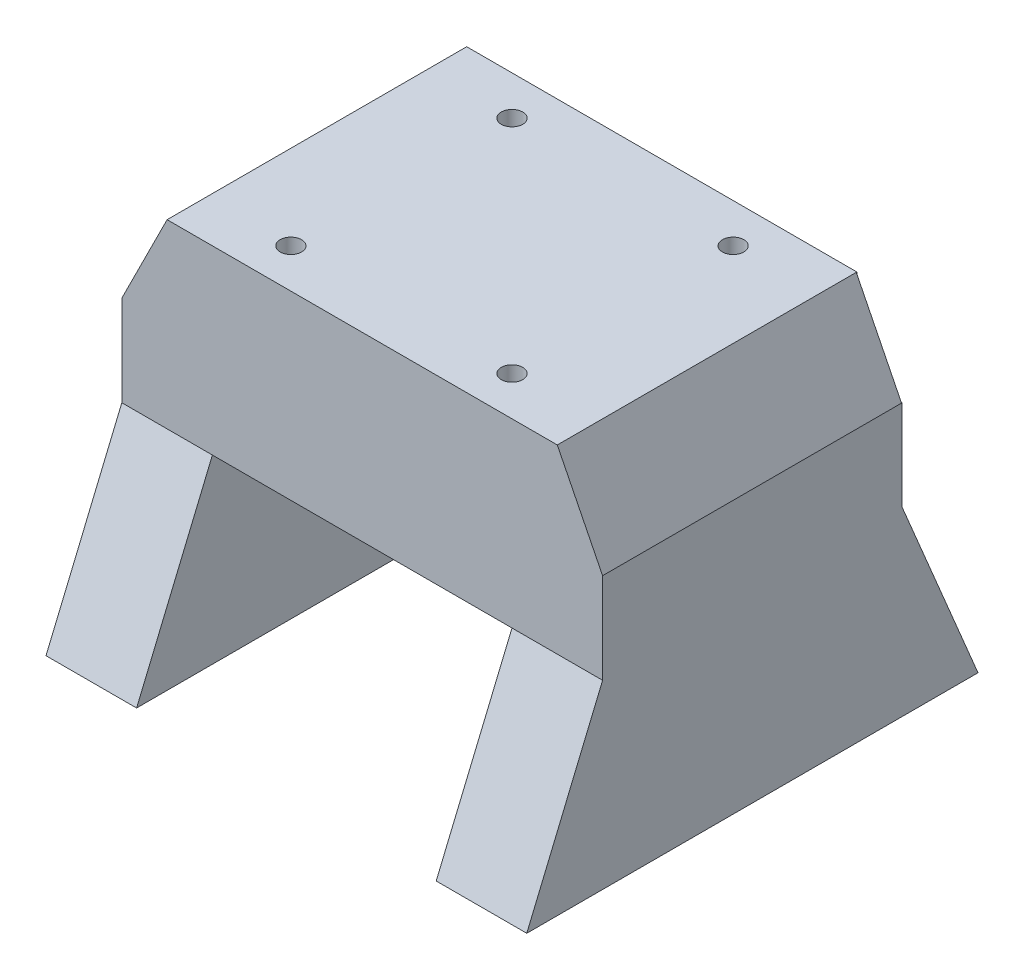
SolidWorks part; units mm, degrees
ref_plane "Front Plane" through (0, 0, 0) normal (0, 0, 1) x (1, 0, 0)
ref_plane "Top Plane" through (0, 0, 0) normal (0, 1, 0) x (1, 0, 0)
ref_plane "Right Plane" through (0, 0, 0) normal (1, 0, 0) x (0, 0, -1)
sketch "Sketch1" plane through (0, 0, 0) normal (0, 1, 0) x (1, 0, 0)
  line L5 (21, 21) -> (-21, -21) construction
  line L6 (21, -21) -> (-21, 21) construction
  line L7 (-27.35, 21) -> (27.35, 21)
  line L8 (-27.35, 21) -> (-27.35, -21)
  line L9 (-27.35, -21) -> (27.35, -21)
  line L10 (27.35, 21) -> (27.35, -21)
  line L11 (-27.35, 21) -> (27.35, -21) construction
  line L12 (-27.35, -21) -> (27.35, 21) construction
  circle A0 centre (-15.5, 15.5) radius 1.5
  circle A1 centre (15.5, 15.5) radius 1.5
  circle A2 centre (15.5, -15.5) radius 1.5
  circle A3 centre (-15.5, -15.5) radius 1.5
  point P0 (0, 0)
  point P14 (0, 0)
  dimension "D1" = 3
  dimension "D2" = 42
  dimension "D3" = 31
  dimension "D4" = 31
  dimension "D5" = 54.7
  dimension "42mm" = 42
extrude "Boss-Extrude1" add sketch "Sketch1" along normal blind 25.4
sketch "Sketch3" plane through (27.35, 0, 0) normal (1, 0, 0) x (0, 0, -1)
  line L0 (21, 25.4) -> (21, 0) construction
  line L1 (-21, 0) -> (21, 0)
  line L2 (-21, 0) -> (-21, 12.7)
  line L3 (-21, 12.7) -> (21, 12.7)
  line L4 (21, 0) -> (21, 12.7)
  line L5 (-21, 0) -> (-31.6282, -25.4)
  line L6 (-31.6282, -25.4) -> (31.6282, -25.4)
  line L7 (31.6282, -25.4) -> (21, 0)
  point P7 (-31.6282, -25.4)
  line M4 (-21, 0) -> (21, 0)
  line M5 (21, 0) -> (21, 25.4)
  line M7 (-21, 25.4) -> (-21, 0)
  dimension "D1" = 12.7
  dimension "D2" = 25.4
extrude "Boss-Extrude4" add sketch "Sketch3" along normal mid plane 12.7 contours L3 M7 M4 M5 | L6 L7 L5 M4 region at (27.35, 6.35, 0) region at (27.35, -13.5549, 0)
extrude "Boss-Extrude5" add sketch "Sketch3<3>" along normal mid plane 12.7 from offset 54.7 contours L6 L7 L5 M4 | L3 M7 M4 M5 region at (27.35, 6.35, 0) region at (27.35, -13.5549, 0) offset against normal yes
sketch "Sketch3<3>" plane through (27.35, 0, 0) normal (1, 0, 0) x (0, 0, -1) same geometry as "Sketch3"
sketch "Sketch4" plane through (0, 0, 21) normal (0, 0, 1) x (1, 0, 0)
  line L0 (-27.35, 12.7) -> (-33.7, 12.7)
  line L1 (-33.7, 12.7) -> (-27.35, 25.4)
  line L2 (27.35, 25.4) -> (27.35, 12.7)
  line L3 (27.35, 12.7) -> (33.7, 12.7)
  line L4 (33.7, 12.7) -> (27.35, 25.4)
  line M1 (-27.35, 25.4) -> (-27.35, 12.7)
  line M2 (-27.35, 12.7) -> (-33.7, 12.7)
  line M8 (33.7, 12.7) -> (27.35, 12.7)
  line M9 (27.35, 12.7) -> (27.35, 25.4)
extrude "Boss-Extrude6" add sketch "Sketch4" against normal blind 41.91 contours L1 M2 M1 | L4 M8 M9 region at (-29.4667, 16.9333, 21) region at (29.4667, 16.9333, 21)
